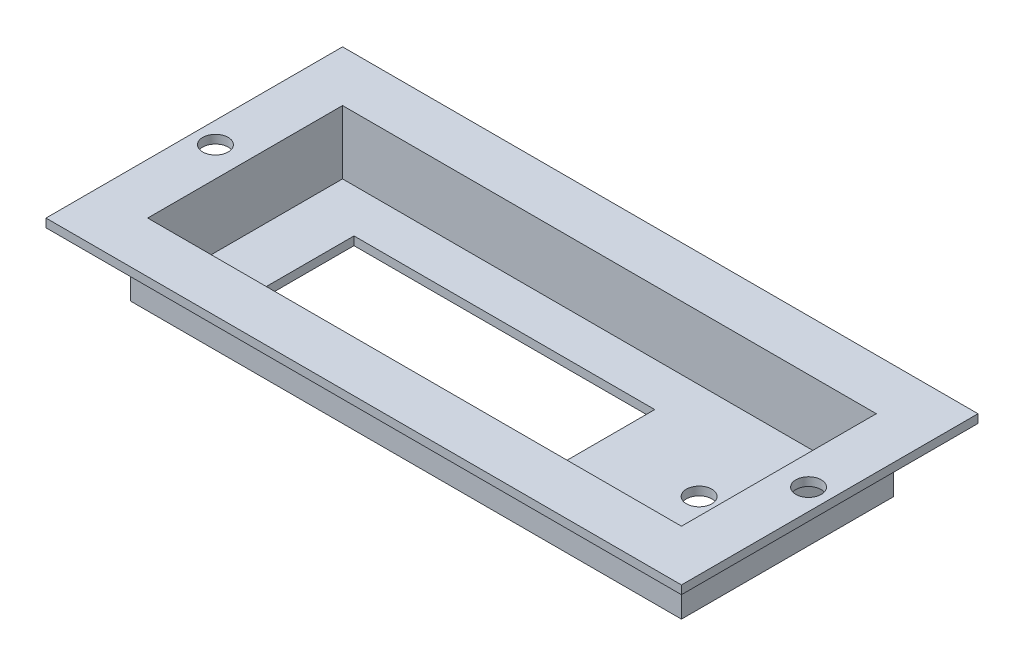
SolidWorks part; units mm, degrees
ref_plane "Alzado" through (0, 0, 0) normal (0, 0, 1) x (1, 0, 0)
ref_plane "Planta" through (0, 0, 0) normal (0, 1, 0) x (1, 0, 0)
ref_plane "Vista lateral" through (0, 0, 0) normal (1, 0, 0) x (0, 0, -1)
sketch "Croquis1" plane through (0, 0, 0) normal (0, 1, 0) x (1, 0, 0)
  line L1 (-65, -25) -> (65, -25)
  line L2 (-65, -25) -> (-65, 25)
  line L3 (-65, 25) -> (65, 25)
  line L4 (65, -25) -> (65, 25)
  line L5 (-65, -25) -> (65, 25) construction
  line L6 (-65, 25) -> (65, -25) construction
  point P0 (0, 0)
  dimension "D1" = 50
  dimension "D2" = 130
extrude "Saliente-Extruir1" add sketch "Croquis1" along normal blind 30
sketch "Croquis2" plane through (0, 30, 0) normal (0, 1, 0) x (1, 0, 0)
  line L1 (-63, -23) -> (63, -23)
  line L2 (-63, -23) -> (-63, 23)
  line L3 (-63, 23) -> (63, 23)
  line L4 (63, -23) -> (63, 23)
  line L5 (-63, -23) -> (63, 23) construction
  line L6 (-63, 23) -> (63, -23) construction
  point P0 (0, 0)
  dimension "D1" = 46
  dimension "D2" = 126
extrude "Cortar-Extruir1" cut sketch "Croquis2" against normal blind 28
sketch "Croquis3" plane through (0, 0, 0) normal (0, -1, 0) x (1, 0, 0)
  line L0 (65, 25) -> (65, -25) construction
  line L1 (-50, -12.7001) -> (21, -12.7001)
  line L2 (-50, -12.7001) -> (-50, 11.7999)
  line L3 (-50, 11.7999) -> (21, 11.7999)
  line L4 (21, -12.7001) -> (21, 11.7999)
  line L9 (-65, -25) -> (-65, 25) construction
  circle A0 centre (43.9981, -0.1735) radius 3
  point P6 (65, 0)
  dimension "D1" = 22.9981
  dimension "D2" = 21.0019
  dimension "D3" = 15
extrude "Cortar-Extruir2" cut sketch "Croquis3" against normal up to surface (2 mm away) up to face at (0, 2, 0)
sketch "Croquis9" plane through (0, 30, 0) normal (0, 1, 0) x (1, 0, 0)
  line L1 (75, -35) -> (-75, -35)
  line L2 (75, -35) -> (75, 35)
  line L3 (75, 35) -> (-75, 35)
  line L4 (-75, -35) -> (-75, 35)
  line L5 (75, -35) -> (-75, 35) construction
  line L6 (75, 35) -> (-75, -35) construction
  line L7 (-65, -25) -> (65, -25)
  line L8 (-65, -25) -> (-65, 25)
  line L9 (-65, 25) -> (65, 25)
  line L10 (65, -25) -> (65, 25)
  line L11 (-65, -25) -> (65, 25) construction
  line L12 (-65, 25) -> (65, -25) construction
  point P0 (0, 0)
  point P6 (0, 0)
extrude "Saliente-Extruir3" add sketch "Croquis9" against normal blind 15
extrude "Cortar-Extruir5" cut sketch "Croquis9<2>" against normal blind 13
sketch "Croquis9<2>" plane through (0, 30, 0) normal (0, 1, 0) x (1, 0, 0) same geometry as "Croquis9"
sketch "Croquis11" plane through (0, 17, 0) normal (0, 1, 0) x (1, 0, 0)
  line L0 (-65, 25) -> (-65, -25) construction
  line L2 (65, -25) -> (65, 25) construction
  circle A0 centre (-70, 0) radius 3
  circle A1 centre (70, 0) radius 3
  point P4 (-65, 0)
  point P7 (65, 0)
  dimension "D1" = 5
  dimension "D2" = 5
extrude "Cortar-Extruir6" cut sketch "Croquis11" against normal up to surface (2 mm away) up to face at (0, 15, 0)
sketch "Croquis12" plane through (-65, 0, 0) normal (-1, 0, 0) x (0, 0, 1)
  line L1 (-25, 17) -> (25, 17)
  line L2 (-25, 17) -> (-25, 30)
  line L3 (-25, 30) -> (25, 30)
  line L4 (25, 17) -> (25, 30)
extrude "Cortar-Extruir7" cut sketch "Croquis12" against normal up to surface (130 mm away) up to face at (65, 23.5, 0)
